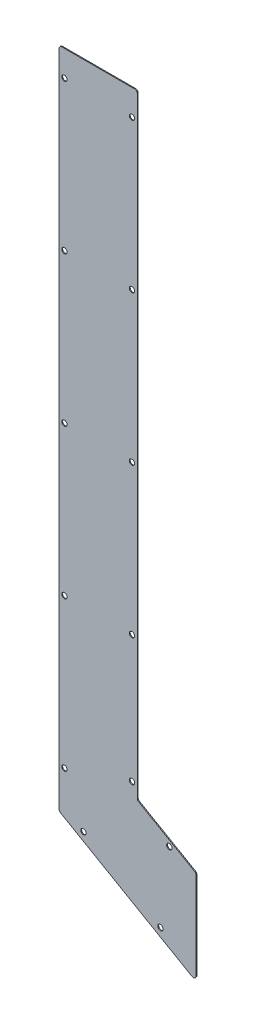
SolidWorks part; units mm, degrees
ref_plane "Front Plane" through (0, 0, 0) normal (0, 0, 1) x (1, 0, 0)
ref_plane "Top Plane" through (0, 0, 0) normal (0, 1, 0) x (1, 0, 0)
ref_plane "Right Plane" through (0, 0, 0) normal (1, 0, 0) x (0, 0, -1)
sketch "Sketch1" plane through (0, 0, 0) normal (0, 0, 1) x (1, 0, 0)
  line L0 (104, 853) -> (16, 853)
  line L1 (16, 853) -> (16, 107.1519)
  line L3 (104, 161.74) -> (104, 853)
  line L4 (104, 161.74) -> (170, 123.6349)
  line L5 (170, 123.6349) -> (170, 18.24)
  line L7 (170, 18.24) -> (16, 107.1519)
  dimension "D1" = 88
  dimension "D2" = 834.76
  dimension "D3" = 60
  dimension "D4" = 143.5
  dimension "D5" = 66
  dimension "D6" = 60
base flange "Base-Flange1" sketch "Sketch1" thickness 1 reverse thickness direction no parameters "D1"=2
sketch "Sketch2" plane through (0, 0, -1) normal (0, 0, -1) x (-1, 0, 0)
  line L0 (-16, 853) -> (-16, 107.1519) construction
  line L1 (-104, 853) -> (-16, 853) construction
  line L2 (-170, 18.24) -> (-170, 123.6349) construction
  line L4 (-130, 50.7349) -> (-43.3975, 100.7349) construction
  line L5 (-16, 107.1519) -> (-170, 18.24) construction
  line L6 (-170, 123.6349) -> (-151.7357, 123.6349) construction
  circle A0 centre (-22, 824) radius 3
  circle A1 centre (-98, 824) radius 3
  circle A2 centre (-98, 656) radius 3
  circle A3 centre (-98, 488) radius 3
  circle A4 centre (-98, 320) radius 3
  circle A8 centre (-22, 656) radius 3
  circle A9 centre (-22, 488) radius 3
  circle A10 centre (-22, 320) radius 3
  circle A11 centre (-22, 152) radius 3
  circle A12 centre (-98, 152) radius 3 [skipped]
  circle A13 centre (-98, 177) radius 3
  circle A14 centre (-140, 134.5649) radius 3
  circle A15 centre (-130, 50.7349) radius 3
  circle A16 centre (-43.3975, 100.7349) radius 3
  dimension "D1" = 6
  dimension "D2" = 6
  dimension "D3" = 29
  dimension "D6" = 15.26
  dimension "D7" = 30
  dimension "D8" = 10.93
  dimension "D9" = 72.9
  dimension "D11" = 40
  dimension "D10" = 100
  dimension "D4" = 2
  dimension "D5" = 5
extrude "Cut-Extrude1" cut sketch "Sketch2" against normal blind 10 normal cut yes
fillet "Fillet1" radius 3 6 edges at (104, 161.74, -0.5) (170, 123.6349, -0.5) (16, 853, -0.5) (104, 853, -0.5) (16, 107.1519, -0.5) (170, 18.24, -0.5)
sketch "Bend-Lines1" [suppressed] plane through (0, 0, 0) normal (0, 1, 0) x (1, 0, 0)
sketch "Bounding-Box1" [suppressed] plane through (0, 0, 0) normal (0, 1, 0) x (1, 0, 0)
sheet metal parameters "Sheet-Metal1" thickness 1 parameters "D1"=2
flat pattern "Flat-Pattern1" [suppressed]
sketch "Bend-Lines2" plane through (0, 0, 0) normal (0, 1, 0) x (1, 0, 0)
sketch3d "Bounding-Box2" [suppressed]
  line L0 (162, 1047, 0) -> (162, 0, 0) construction
  line L1 (0, 1047, 0) -> (0, 0, 0) construction
  line L2 (162, 1047, 0) -> (0, 1047, 0) construction
  line L3 (162, 0, 0) -> (0, 0, 0) construction
sheet metal parameters "Sheet-Metal2" thickness 1 parameters "D1"=2
flat pattern "Flat-Pattern1"
sketch "Bend-Lines2" plane through (0, 0, 0) normal (0, 1, 0) x (1, 0, 0)
sketch3d "Bounding-Box2" [suppressed]
  line L0 (170, 20.4363, 0) -> (170, 853, 0) construction
  line L1 (16, 20.4363, 0) -> (16, 853, 0) construction
  line L2 (170, 20.4363, 0) -> (16, 20.4363, 0) construction
  line L3 (170, 853, 0) -> (16, 853, 0) construction
